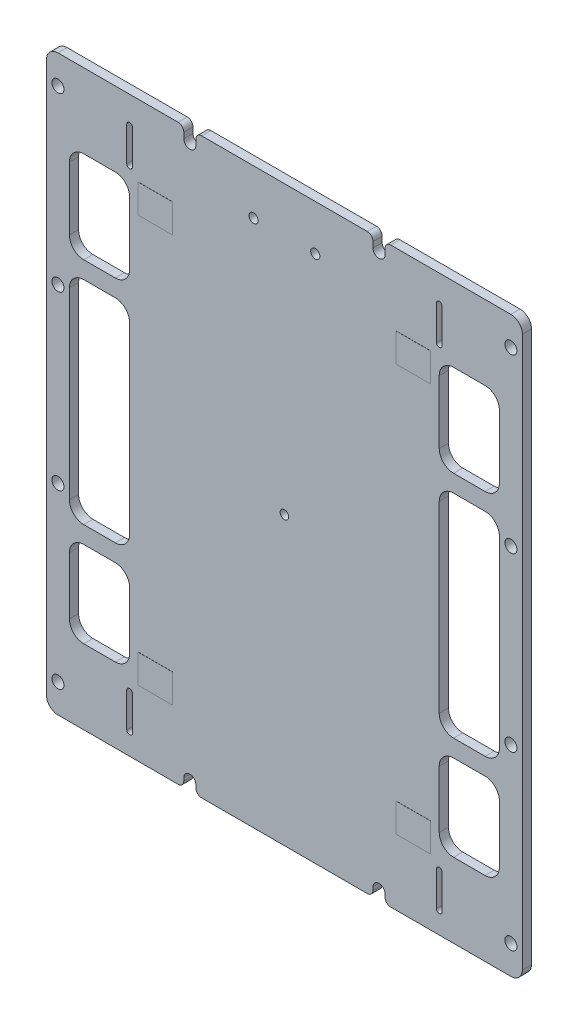
SolidWorks part; units mm, degrees
material "FR4_stuffedProtoboard"
ref_plane "Front Plane" through (0, 0, 0) normal (0, 0, 1) x (1, 0, 0)
ref_plane "Top Plane" through (0, 0, 0) normal (0, 1, 0) x (1, 0, 0)
ref_plane "Right Plane" through (0, 0, 0) normal (1, 0, 0) x (0, 0, -1)
sketch "Sketch1" plane through (0, 0, 0) normal (0, 0, 1) x (1, 0, 0)
  line L1 (-39.5, -50) -> (39.5, -50)
  line L2 (-41.5, -48) -> (-41.5, 48)
  line L3 (-39.5, 50) -> (39.5, 50)
  line L4 (41.5, -48) -> (41.5, 48)
  line L5 (-41.5, -50) -> (41.5, 50) construction
  line L6 (-41.5, 50) -> (41.5, -50) construction
  arc A0 (-39.5, -50) -> (-41.5, -48) centre (-39.5, -48) cw
  arc A1 (39.5, -50) -> (41.5, -48) centre (39.5, -48) ccw
  arc A2 (39.5, 50) -> (41.5, 48) centre (39.5, 48) cw
  arc A3 (-41.5, 48) -> (-39.5, 50) centre (-39.5, 48) cw
  point P0 (0, 0)
  dimension "D3" = 2
  dimension "D1" = 100
  dimension "D2" = 83
extrude "boardOutline" add sketch "Sketch1" along normal blind 1.6
sketch "Sketch2" plane through (0, 0, 1.6) normal (0, 0, 1) x (1, 0, 0)
  line L0 (39.5, 50) -> (-39.5, 50) construction
  line L1 (-41.5, 48) -> (-41.5, -48) construction
  line L2 (-5.385, 42.1) -> (5.385, 42.1) construction
  line L3 (-38, 44.2) -> (-38, 4.2) construction
  line L4 (0, 42.1) -> (0, 50) construction
  circle A0 centre (0, 0) radius 0.75
  circle A1 centre (-38, 44.2) radius 1.05 construction
  circle A2 centre (37.5, 44.2) radius 1.05 construction
  circle A3 centre (37.5, 4.2) radius 1.05 construction
  circle A4 centre (37.5, -35.8) radius 1.05 construction
  circle A5 centre (-38, 4.2) radius 1.05 construction
  circle A6 centre (-38, -35.8) radius 1.05 construction
  circle A7 centre (-5.385, 42.1) radius 0.8
  circle A8 centre (5.385, 42.1) radius 0.8
  dimension "D1" = 1.5
  dimension "D2" = 2.1
  dimension "D9" = 10.77
  dimension "D7" = 1.6
  dimension "D11" = 7.9
  dimension "D3" = 5.8
  dimension "D4" = 3.5
  dimension "D8" = 40
  dimension "D10" = 37.5
  dimension "D5" = 2
  dimension "D6" = 3
extrude "componentHoles" cut sketch "Sketch2" against normal through all
sketch "Sketch4" plane through (0, 0, 1.6) normal (0, 0, 1) x (1, 0, 0)
  line L0 (-27, 39.25) -> (-27, 45.25) construction
  line L1 (-27.5, 39.25) -> (-27.5, 45.25)
  line L2 (-26.5, 39.25) -> (-26.5, 45.25)
  line L3 (39.5, 50) -> (-39.5, 50) construction
  line L4 (-41.5, 48) -> (-41.5, -48) construction
  line L5 (27, 39.25) -> (27, 45.25) construction
  line L6 (26.5, 39.25) -> (26.5, 45.25)
  line L7 (27.5, 39.25) -> (27.5, 45.25)
  line L8 (27, -46.25) -> (27, -40.25) construction
  line L9 (26.5, -46.25) -> (26.5, -40.25)
  line L10 (27.5, -46.25) -> (27.5, -40.25)
  line L11 (-27, -46.25) -> (-27, -40.25) construction
  line L12 (-27.5, -46.25) -> (-27.5, -40.25)
  line L13 (-26.5, -46.25) -> (-26.5, -40.25)
  line L14 (-27, 39.25) -> (27, 39.25) construction
  line L15 (0, 39.25) -> (0, 50) construction
  arc A0 (-27.5, 39.25) -> (-26.5, 39.25) centre (-27, 39.25) ccw
  arc A1 (-26.5, 45.25) -> (-27.5, 45.25) centre (-27, 45.25) ccw
  arc A2 (26.5, 39.25) -> (27.5, 39.25) centre (27, 39.25) ccw
  arc A3 (27.5, 45.25) -> (26.5, 45.25) centre (27, 45.25) ccw
  arc A4 (26.5, -46.25) -> (27.5, -46.25) centre (27, -46.25) ccw
  arc A5 (27.5, -40.25) -> (26.5, -40.25) centre (27, -40.25) ccw
  arc A6 (-27.5, -46.25) -> (-26.5, -46.25) centre (-27, -46.25) ccw
  arc A7 (-26.5, -40.25) -> (-27.5, -40.25) centre (-27, -40.25) ccw
  point P2 (-27, 42.25)
  point P16 (27, 42.25)
  point P23 (27, -43.25)
  point P30 (-27, -43.25)
  dimension "D1" = 4.75
  dimension "D2" = 14
  dimension "D3" = 1
  dimension "D4" = 6
  dimension "D7" = 54
  dimension "D9" = 79.5
  dimension "D5" = 2
  dimension "D6" = 2
extrude "solarCellContactHoles" cut sketch "Sketch4" against normal blind 1.6
sketch "FrameLattice" plane through (0, 0, 0) normal (0, 0, 1) x (1, 0, 0)
  line L4 (-12.5, -19) -> (12.5, -19)
  line L5 (15, -16.5) -> (15, 15.5)
  line L6 (12.5, 18) -> (-12.5, 18)
  line L7 (-15, 15.5) -> (-15, -16.5)
  line L8 (-12.5, -19) -> (12.5, -19)
  line L9 (15, -16.5) -> (15, 15.5)
  line L10 (12.5, 18) -> (-12.5, 18)
  line L11 (-15, 15.5) -> (-15, -16.5)
  line L12 (-12.5, -92) -> (12.5, -92)
  line L13 (15, -89.5) -> (15, -69.5)
  line L14 (12.5, -67) -> (-12.5, -67)
  line L15 (-15, -69.5) -> (-15, -89.5)
  line L16 (-12.5, -92) -> (12.5, -92)
  line L17 (15, -89.5) -> (15, -69.5)
  line L18 (12.5, -67) -> (-12.5, -67)
  line L19 (-15, -69.5) -> (-15, -89.5)
  line L20 (-35, -132) -> (-20.5, -132)
  line L21 (-18, -129.5) -> (-18, -97.5)
  line L22 (-20.5, -95) -> (-35, -95)
  line L23 (-37.5, -97.5) -> (-37.5, -129.5)
  line L24 (-35, -132) -> (-20.5, -132)
  line L25 (-18, -129.5) -> (-18, -97.5)
  line L26 (-20.5, -95) -> (-35, -95)
  line L27 (-37.5, -97.5) -> (-37.5, -129.5)
  line L28 (20.5, -160) -> (35, -160)
  line L29 (37.5, -157.5) -> (37.5, -137.5)
  line L30 (35, -135) -> (20.5, -135)
  line L31 (18, -137.5) -> (18, -157.5)
  line L32 (20.5, -160) -> (35, -160)
  line L33 (37.5, -157.5) -> (37.5, -137.5)
  line L34 (35, -135) -> (20.5, -135)
  line L35 (18, -137.5) -> (18, -157.5)
  line L36 (20.5, -92) -> (35, -92)
  line L37 (37.5, -89.5) -> (37.5, -69.5)
  line L38 (35, -67) -> (20.5, -67)
  line L39 (18, -69.5) -> (18, -89.5)
  line L40 (20.5, -92) -> (35, -92)
  line L41 (37.5, -89.5) -> (37.5, -69.5)
  line L42 (35, -67) -> (20.5, -67)
  line L43 (18, -69.5) -> (18, -89.5)
  line L44 (-35, -92) -> (-20.5, -92)
  line L45 (-18, -89.5) -> (-18, -69.5)
  line L46 (-20.5, -67) -> (-35, -67)
  line L47 (-37.5, -69.5) -> (-37.5, -89.5)
  line L48 (-35, -92) -> (-20.5, -92)
  line L49 (-18, -89.5) -> (-18, -69.5)
  line L50 (-20.5, -67) -> (-35, -67)
  line L51 (-37.5, -69.5) -> (-37.5, -89.5)
  line L52 (20.5, -132) -> (35, -132)
  line L53 (37.5, -129.5) -> (37.5, -97.5)
  line L54 (35, -95) -> (20.5, -95)
  line L55 (18, -97.5) -> (18, -129.5)
  line L56 (20.5, -132) -> (35, -132)
  line L57 (37.5, -129.5) -> (37.5, -97.5)
  line L58 (35, -95) -> (20.5, -95)
  line L59 (18, -97.5) -> (18, -129.5)
  line L60 (-12.5, -160) -> (12.5, -160)
  line L61 (15, -157.5) -> (15, -137.5)
  line L62 (12.5, -135) -> (-12.5, -135)
  line L63 (-15, -137.5) -> (-15, -157.5)
  line L65 (15, -157.5) -> (15, -137.5)
  line L66 (12.5, -135) -> (-12.5, -135)
  line L67 (-15, -137.5) -> (-15, -157.5)
  line L68 (-26.75, -61.5) -> (-26.75, -52.5)
  line L69 (-29.25, -50) -> (-34.5, -50)
  line L70 (-37, -52.5) -> (-37, -61.5)
  line L71 (-34.5, -64) -> (-29.25, -64)
  line L72 (-26.75, -61.5) -> (-26.75, -52.5)
  line L73 (-29.25, -50) -> (-34.5, -50)
  line L74 (-37, -52.5) -> (-37, -61.5)
  line L75 (-34.5, -64) -> (-29.25, -64)
  line L76 (-35, -160) -> (-20.5, -160)
  line L77 (-18, -157.5) -> (-18, -137.5)
  line L78 (-20.5, -135) -> (-35, -135)
  line L79 (-37.5, -137.5) -> (-37.5, -157.5)
  line L80 (-35, -160) -> (-20.5, -160)
  line L81 (-18, -157.5) -> (-18, -137.5)
  line L82 (-20.5, -135) -> (-35, -135)
  line L83 (-37.5, -137.5) -> (-37.5, -157.5)
  line L84 (-12.5, -132) -> (12.5, -132)
  line L85 (15, -129.5) -> (15, -97.5)
  line L86 (12.5, -95) -> (-12.5, -95)
  line L87 (-15, -97.5) -> (-15, -129.5)
  line L88 (-12.5, -132) -> (12.5, -132)
  line L89 (15, -129.5) -> (15, -97.5)
  line L90 (12.5, -95) -> (-12.5, -95)
  line L91 (-15, -97.5) -> (-15, -129.5)
  line L92 (-35, -19) -> (-20.5, -19)
  line L93 (-18, -16.5) -> (-18, 15.5)
  line L94 (-20.5, 18) -> (-35, 18)
  line L95 (-37.5, 15.5) -> (-37.5, -16.5)
  line L96 (-35, -19) -> (-20.5, -19)
  line L97 (-18, -16.5) -> (-18, 15.5)
  line L98 (-20.5, 18) -> (-35, 18)
  line L99 (-37.5, 15.5) -> (-37.5, -16.5)
  line L100 (20.5, -47) -> (35, -47)
  line L101 (37.5, -44.5) -> (37.5, -24.5)
  line L102 (35, -22) -> (20.5, -22)
  line L103 (18, -24.5) -> (18, -44.5)
  line L104 (20.5, -47) -> (35, -47)
  line L105 (37.5, -44.5) -> (37.5, -24.5)
  line L106 (35, -22) -> (20.5, -22)
  line L107 (18, -24.5) -> (18, -44.5)
  line L108 (-12.5, -47) -> (12.5, -47)
  line L109 (15, -44.5) -> (15, -24.5)
  line L110 (12.5, -22) -> (-12.5, -22)
  line L111 (-15, -24.5) -> (-15, -44.5)
  line L112 (-12.5, -47) -> (12.5, -47)
  line L113 (15, -44.5) -> (15, -24.5)
  line L114 (12.5, -22) -> (-12.5, -22)
  line L115 (-15, -24.5) -> (-15, -44.5)
  line L116 (-35, -47) -> (-20.5, -47)
  line L117 (-18, -44.5) -> (-18, -24.5)
  line L118 (-20.5, -22) -> (-35, -22)
  line L119 (-37.5, -24.5) -> (-37.5, -44.5)
  line L120 (-35, -47) -> (-20.5, -47)
  line L121 (-18, -44.5) -> (-18, -24.5)
  line L122 (-20.5, -22) -> (-35, -22)
  line L123 (-37.5, -24.5) -> (-37.5, -44.5)
  line L124 (20.5, -19) -> (35, -19)
  line L125 (37.5, -16.5) -> (37.5, 15.5)
  line L126 (35, 18) -> (20.5, 18)
  line L127 (18, 15.5) -> (18, -16.5)
  line L128 (20.5, -19) -> (35, -19)
  line L129 (37.5, -16.5) -> (37.5, 15.5)
  line L130 (35, 18) -> (20.5, 18)
  line L131 (18, 15.5) -> (18, -16.5)
  line L132 (-35, 21) -> (-20.5, 21)
  line L133 (-18, 23.5) -> (-18, 43.5)
  line L134 (-20.5, 46) -> (-35, 46)
  line L135 (-37.5, 43.5) -> (-37.5, 23.5)
  line L136 (-35, 21) -> (-20.5, 21)
  line L137 (-18, 23.5) -> (-18, 43.5)
  line L138 (-20.5, 46) -> (-35, 46)
  line L139 (-37.5, 43.5) -> (-37.5, 23.5)
  line L140 (-12.5, 21) -> (12.5, 21)
  line L141 (15, 23.5) -> (15, 43.5)
  line L142 (12.5, 46) -> (-12.5, 46)
  line L143 (-15, 43.5) -> (-15, 23.5)
  line L144 (-12.5, 21) -> (12.5, 21)
  line L145 (15, 23.5) -> (15, 43.5)
  line L147 (-15, 43.5) -> (-15, 23.5)
  line L148 (20.5, 21) -> (35, 21)
  line L149 (37.5, 23.5) -> (37.5, 43.5)
  line L150 (35, 46) -> (20.5, 46)
  line L151 (18, 43.5) -> (18, 23.5)
  line L152 (20.5, 21) -> (35, 21)
  line L153 (37.5, 23.5) -> (37.5, 43.5)
  line L154 (35, 46) -> (20.5, 46)
  line L155 (18, 43.5) -> (18, 23.5)
  line L156 (-3.5, -61.5) -> (-3.5, -52.5)
  line L157 (-6, -50) -> (-12.5, -50)
  line L158 (-15, -52.5) -> (-15, -61.5)
  line L159 (-12.5, -64) -> (-6, -64)
  line L160 (-3.5, -61.5) -> (-3.5, -52.5)
  line L161 (-6, -50) -> (-12.5, -50)
  line L162 (-15, -52.5) -> (-15, -61.5)
  line L163 (-12.5, -64) -> (-6, -64)
  line L164 (29.25, -64) -> (34.5, -64)
  line L165 (37, -61.5) -> (37, -52.5)
  line L166 (34.5, -50) -> (29.25, -50)
  line L167 (26.75, -52.5) -> (26.75, -61.5)
  line L168 (29.25, -64) -> (34.5, -64)
  line L169 (37, -61.5) -> (37, -52.5)
  line L170 (34.5, -50) -> (29.25, -50)
  line L171 (26.75, -52.5) -> (26.75, -61.5)
  line L172 (6, -64) -> (12.5, -64)
  line L173 (15, -61.5) -> (15, -52.5)
  line L174 (12.5, -50) -> (6, -50)
  line L175 (3.5, -52.5) -> (3.5, -61.5)
  line L176 (6, -64) -> (12.5, -64)
  line L177 (15, -61.5) -> (15, -52.5)
  line L178 (12.5, -50) -> (6, -50)
  line L179 (3.5, -52.5) -> (3.5, -61.5)
  line L212 (-12.5, -160) -> (12.5, -160)
  line L213 (12.5, 46) -> (-12.5, 46)
  circle A2 centre (-16.5, 48) radius 0.8
  circle A3 centre (-16.5, 48) radius 0.8
  circle A4 centre (-16.5, -162) radius 0.8
  arc A5 (12.5, -19) -> (15, -16.5) centre (12.5, -16.5) ccw
  arc A6 (15, 15.5) -> (12.5, 18) centre (12.5, 15.5) ccw
  arc A7 (-12.5, 18) -> (-15, 15.5) centre (-12.5, 15.5) ccw
  arc A8 (-15, -16.5) -> (-12.5, -19) centre (-12.5, -16.5) ccw
  arc A9 (12.5, -19) -> (15, -16.5) centre (12.5, -16.5) ccw
  arc A10 (15, 15.5) -> (12.5, 18) centre (12.5, 15.5) ccw
  arc A11 (-12.5, 18) -> (-15, 15.5) centre (-12.5, 15.5) ccw
  arc A12 (-15, -16.5) -> (-12.5, -19) centre (-12.5, -16.5) ccw
  arc A13 (12.5, -92) -> (15, -89.5) centre (12.5, -89.5) ccw
  arc A14 (15, -69.5) -> (12.5, -67) centre (12.5, -69.5) ccw
  arc A15 (-12.5, -67) -> (-15, -69.5) centre (-12.5, -69.5) ccw
  arc A16 (-15, -89.5) -> (-12.5, -92) centre (-12.5, -89.5) ccw
  arc A17 (12.5, -92) -> (15, -89.5) centre (12.5, -89.5) ccw
  arc A18 (15, -69.5) -> (12.5, -67) centre (12.5, -69.5) ccw
  arc A19 (-12.5, -67) -> (-15, -69.5) centre (-12.5, -69.5) ccw
  arc A20 (-15, -89.5) -> (-12.5, -92) centre (-12.5, -89.5) ccw
  arc A21 (-20.5, -132) -> (-18, -129.5) centre (-20.5, -129.5) ccw
  arc A22 (-18, -97.5) -> (-20.5, -95) centre (-20.5, -97.5) ccw
  arc A23 (-35, -95) -> (-37.5, -97.5) centre (-35, -97.5) ccw
  arc A24 (-37.5, -129.5) -> (-35, -132) centre (-35, -129.5) ccw
  arc A25 (-20.5, -132) -> (-18, -129.5) centre (-20.5, -129.5) ccw
  arc A26 (-18, -97.5) -> (-20.5, -95) centre (-20.5, -97.5) ccw
  arc A27 (-35, -95) -> (-37.5, -97.5) centre (-35, -97.5) ccw
  arc A28 (-37.5, -129.5) -> (-35, -132) centre (-35, -129.5) ccw
  arc A29 (35, -160) -> (37.5, -157.5) centre (35, -157.5) ccw
  arc A30 (37.5, -137.5) -> (35, -135) centre (35, -137.5) ccw
  arc A31 (20.5, -135) -> (18, -137.5) centre (20.5, -137.5) ccw
  arc A32 (18, -157.5) -> (20.5, -160) centre (20.5, -157.5) ccw
  arc A33 (35, -160) -> (37.5, -157.5) centre (35, -157.5) ccw
  arc A34 (37.5, -137.5) -> (35, -135) centre (35, -137.5) ccw
  arc A35 (20.5, -135) -> (18, -137.5) centre (20.5, -137.5) ccw
  arc A36 (18, -157.5) -> (20.5, -160) centre (20.5, -157.5) ccw
  arc A37 (35, -92) -> (37.5, -89.5) centre (35, -89.5) ccw
  arc A38 (37.5, -69.5) -> (35, -67) centre (35, -69.5) ccw
  arc A39 (20.5, -67) -> (18, -69.5) centre (20.5, -69.5) ccw
  arc A40 (18, -89.5) -> (20.5, -92) centre (20.5, -89.5) ccw
  arc A41 (35, -92) -> (37.5, -89.5) centre (35, -89.5) ccw
  arc A42 (37.5, -69.5) -> (35, -67) centre (35, -69.5) ccw
  arc A43 (20.5, -67) -> (18, -69.5) centre (20.5, -69.5) ccw
  arc A44 (18, -89.5) -> (20.5, -92) centre (20.5, -89.5) ccw
  arc A45 (-20.5, -92) -> (-18, -89.5) centre (-20.5, -89.5) ccw
  arc A46 (-18, -69.5) -> (-20.5, -67) centre (-20.5, -69.5) ccw
  arc A47 (-35, -67) -> (-37.5, -69.5) centre (-35, -69.5) ccw
  arc A48 (-37.5, -89.5) -> (-35, -92) centre (-35, -89.5) ccw
  arc A49 (-20.5, -92) -> (-18, -89.5) centre (-20.5, -89.5) ccw
  arc A50 (-18, -69.5) -> (-20.5, -67) centre (-20.5, -69.5) ccw
  arc A51 (-35, -67) -> (-37.5, -69.5) centre (-35, -69.5) ccw
  arc A52 (-37.5, -89.5) -> (-35, -92) centre (-35, -89.5) ccw
  arc A53 (35, -132) -> (37.5, -129.5) centre (35, -129.5) ccw
  arc A54 (37.5, -97.5) -> (35, -95) centre (35, -97.5) ccw
  arc A55 (20.5, -95) -> (18, -97.5) centre (20.5, -97.5) ccw
  arc A56 (18, -129.5) -> (20.5, -132) centre (20.5, -129.5) ccw
  arc A57 (35, -132) -> (37.5, -129.5) centre (35, -129.5) ccw
  arc A58 (37.5, -97.5) -> (35, -95) centre (35, -97.5) ccw
  arc A59 (20.5, -95) -> (18, -97.5) centre (20.5, -97.5) ccw
  arc A60 (18, -129.5) -> (20.5, -132) centre (20.5, -129.5) ccw
  arc A61 (12.5, -160) -> (15, -157.5) centre (12.5, -157.5) ccw
  arc A62 (15, -137.5) -> (12.5, -135) centre (12.5, -137.5) ccw
  arc A63 (-12.5, -135) -> (-15, -137.5) centre (-12.5, -137.5) ccw
  arc A64 (-15, -157.5) -> (-12.5, -160) centre (-12.5, -157.5) ccw
  arc A65 (12.5, -160) -> (15, -157.5) centre (12.5, -157.5) ccw
  arc A66 (15, -137.5) -> (12.5, -135) centre (12.5, -137.5) ccw
  arc A67 (-12.5, -135) -> (-15, -137.5) centre (-12.5, -137.5) ccw
  arc A68 (-15, -157.5) -> (-12.5, -160) centre (-12.5, -157.5) ccw
  circle A69 centre (-16.5, -162) radius 0.8
  circle A70 centre (16.5, -162) radius 0.8
  circle A71 centre (16.5, -162) radius 0.8
  circle A72 centre (-16.5, -65.5) radius 0.8
  circle A73 centre (-16.5, -65.5) radius 0.8
  circle A74 centre (16.5, -65.5) radius 0.8
  circle A75 centre (16.5, -65.5) radius 0.8
  circle A76 centre (-39.5, -129) radius 0.8
  circle A77 centre (-39.5, -129) radius 0.8
  circle A78 centre (39.5, -159) radius 0.8
  circle A79 centre (39.5, -159) radius 0.8
  circle A80 centre (-39.5, -159) radius 0.8
  circle A81 centre (-39.5, -159) radius 0.8
  circle A82 centre (39.5, -129) radius 0.8
  circle A83 centre (39.5, -129) radius 0.8
  circle A84 centre (39.5, -99) radius 0.8
  circle A85 centre (39.5, -99) radius 0.8
  circle A86 centre (-39.5, -99) radius 0.8
  circle A87 centre (-39.5, -99) radius 0.8
  circle A88 centre (-39.5, -69) radius 0.8
  circle A89 centre (-39.5, -69) radius 0.8
  circle A90 centre (39.5, -69) radius 0.8
  circle A91 centre (39.5, -69) radius 0.8
  circle A92 centre (39.5, -15) radius 0.8
  circle A93 centre (39.5, -15) radius 0.8
  circle A94 centre (39.5, 15) radius 0.8
  arc A95 (-26.75, -52.5) -> (-29.25, -50) centre (-29.25, -52.5) ccw
  arc A96 (-34.5, -50) -> (-37, -52.5) centre (-34.5, -52.5) ccw
  arc A97 (-37, -61.5) -> (-34.5, -64) centre (-34.5, -61.5) ccw
  arc A98 (-29.25, -64) -> (-26.75, -61.5) centre (-29.25, -61.5) ccw
  arc A99 (-26.75, -52.5) -> (-29.25, -50) centre (-29.25, -52.5) ccw
  arc A100 (-34.5, -50) -> (-37, -52.5) centre (-34.5, -52.5) ccw
  arc A101 (-37, -61.5) -> (-34.5, -64) centre (-34.5, -61.5) ccw
  arc A102 (-29.25, -64) -> (-26.75, -61.5) centre (-29.25, -61.5) ccw
  arc A103 (-20.5, -160) -> (-18, -157.5) centre (-20.5, -157.5) ccw
  arc A104 (-18, -137.5) -> (-20.5, -135) centre (-20.5, -137.5) ccw
  arc A105 (-35, -135) -> (-37.5, -137.5) centre (-35, -137.5) ccw
  arc A106 (-37.5, -157.5) -> (-35, -160) centre (-35, -157.5) ccw
  arc A107 (-20.5, -160) -> (-18, -157.5) centre (-20.5, -157.5) ccw
  arc A108 (-18, -137.5) -> (-20.5, -135) centre (-20.5, -137.5) ccw
  arc A109 (-35, -135) -> (-37.5, -137.5) centre (-35, -137.5) ccw
  arc A110 (-37.5, -157.5) -> (-35, -160) centre (-35, -157.5) ccw
  arc A111 (12.5, -132) -> (15, -129.5) centre (12.5, -129.5) ccw
  arc A112 (15, -97.5) -> (12.5, -95) centre (12.5, -97.5) ccw
  arc A113 (-12.5, -95) -> (-15, -97.5) centre (-12.5, -97.5) ccw
  arc A114 (-15, -129.5) -> (-12.5, -132) centre (-12.5, -129.5) ccw
  arc A115 (12.5, -132) -> (15, -129.5) centre (12.5, -129.5) ccw
  arc A116 (15, -97.5) -> (12.5, -95) centre (12.5, -97.5) ccw
  arc A117 (-12.5, -95) -> (-15, -97.5) centre (-12.5, -97.5) ccw
  arc A118 (-15, -129.5) -> (-12.5, -132) centre (-12.5, -129.5) ccw
  arc A119 (-20.5, -19) -> (-18, -16.5) centre (-20.5, -16.5) ccw
  arc A120 (-18, 15.5) -> (-20.5, 18) centre (-20.5, 15.5) ccw
  arc A121 (-35, 18) -> (-37.5, 15.5) centre (-35, 15.5) ccw
  arc A122 (-37.5, -16.5) -> (-35, -19) centre (-35, -16.5) ccw
  arc A123 (-20.5, -19) -> (-18, -16.5) centre (-20.5, -16.5) ccw
  arc A124 (-18, 15.5) -> (-20.5, 18) centre (-20.5, 15.5) ccw
  arc A125 (-35, 18) -> (-37.5, 15.5) centre (-35, 15.5) ccw
  arc A126 (-37.5, -16.5) -> (-35, -19) centre (-35, -16.5) ccw
  arc A127 (35, -47) -> (37.5, -44.5) centre (35, -44.5) ccw
  arc A128 (37.5, -24.5) -> (35, -22) centre (35, -24.5) ccw
  arc A129 (20.5, -22) -> (18, -24.5) centre (20.5, -24.5) ccw
  arc A130 (18, -44.5) -> (20.5, -47) centre (20.5, -44.5) ccw
  arc A131 (35, -47) -> (37.5, -44.5) centre (35, -44.5) ccw
  arc A132 (37.5, -24.5) -> (35, -22) centre (35, -24.5) ccw
  arc A133 (20.5, -22) -> (18, -24.5) centre (20.5, -24.5) ccw
  arc A134 (18, -44.5) -> (20.5, -47) centre (20.5, -44.5) ccw
  arc A135 (12.5, -47) -> (15, -44.5) centre (12.5, -44.5) ccw
  arc A136 (15, -24.5) -> (12.5, -22) centre (12.5, -24.5) ccw
  arc A137 (-12.5, -22) -> (-15, -24.5) centre (-12.5, -24.5) ccw
  arc A138 (-15, -44.5) -> (-12.5, -47) centre (-12.5, -44.5) ccw
  arc A139 (12.5, -47) -> (15, -44.5) centre (12.5, -44.5) ccw
  arc A140 (15, -24.5) -> (12.5, -22) centre (12.5, -24.5) ccw
  arc A141 (-12.5, -22) -> (-15, -24.5) centre (-12.5, -24.5) ccw
  arc A142 (-15, -44.5) -> (-12.5, -47) centre (-12.5, -44.5) ccw
  arc A143 (-20.5, -47) -> (-18, -44.5) centre (-20.5, -44.5) ccw
  arc A144 (-18, -24.5) -> (-20.5, -22) centre (-20.5, -24.5) ccw
  arc A145 (-35, -22) -> (-37.5, -24.5) centre (-35, -24.5) ccw
  arc A146 (-37.5, -44.5) -> (-35, -47) centre (-35, -44.5) ccw
  arc A147 (-20.5, -47) -> (-18, -44.5) centre (-20.5, -44.5) ccw
  arc A148 (-18, -24.5) -> (-20.5, -22) centre (-20.5, -24.5) ccw
  arc A149 (-35, -22) -> (-37.5, -24.5) centre (-35, -24.5) ccw
  arc A150 (-37.5, -44.5) -> (-35, -47) centre (-35, -44.5) ccw
  arc A151 (35, -19) -> (37.5, -16.5) centre (35, -16.5) ccw
  arc A152 (37.5, 15.5) -> (35, 18) centre (35, 15.5) ccw
  arc A153 (20.5, 18) -> (18, 15.5) centre (20.5, 15.5) ccw
  arc A154 (18, -16.5) -> (20.5, -19) centre (20.5, -16.5) ccw
  arc A155 (35, -19) -> (37.5, -16.5) centre (35, -16.5) ccw
  arc A156 (37.5, 15.5) -> (35, 18) centre (35, 15.5) ccw
  arc A157 (20.5, 18) -> (18, 15.5) centre (20.5, 15.5) ccw
  arc A158 (18, -16.5) -> (20.5, -19) centre (20.5, -16.5) ccw
  arc A159 (-20.5, 21) -> (-18, 23.5) centre (-20.5, 23.5) ccw
  arc A160 (-18, 43.5) -> (-20.5, 46) centre (-20.5, 43.5) ccw
  arc A161 (-35, 46) -> (-37.5, 43.5) centre (-35, 43.5) ccw
  arc A162 (-37.5, 23.5) -> (-35, 21) centre (-35, 23.5) ccw
  arc A163 (-20.5, 21) -> (-18, 23.5) centre (-20.5, 23.5) ccw
  arc A164 (-18, 43.5) -> (-20.5, 46) centre (-20.5, 43.5) ccw
  arc A165 (-35, 46) -> (-37.5, 43.5) centre (-35, 43.5) ccw
  arc A166 (-37.5, 23.5) -> (-35, 21) centre (-35, 23.5) ccw
  arc A167 (12.5, 21) -> (15, 23.5) centre (12.5, 23.5) ccw
  arc A168 (15, 43.5) -> (12.5, 46) centre (12.5, 43.5) ccw
  arc A169 (-12.5, 46) -> (-15, 43.5) centre (-12.5, 43.5) ccw
  arc A170 (-15, 23.5) -> (-12.5, 21) centre (-12.5, 23.5) ccw
  arc A171 (12.5, 21) -> (15, 23.5) centre (12.5, 23.5) ccw
  arc A172 (15, 43.5) -> (12.5, 46) centre (12.5, 43.5) ccw
  arc A173 (-12.5, 46) -> (-15, 43.5) centre (-12.5, 43.5) ccw
  arc A174 (-15, 23.5) -> (-12.5, 21) centre (-12.5, 23.5) ccw
  arc A175 (35, 21) -> (37.5, 23.5) centre (35, 23.5) ccw
  arc A176 (37.5, 43.5) -> (35, 46) centre (35, 43.5) ccw
  arc A177 (20.5, 46) -> (18, 43.5) centre (20.5, 43.5) ccw
  arc A178 (18, 23.5) -> (20.5, 21) centre (20.5, 23.5) ccw
  arc A179 (35, 21) -> (37.5, 23.5) centre (35, 23.5) ccw
  arc A180 (37.5, 43.5) -> (35, 46) centre (35, 43.5) ccw
  arc A181 (20.5, 46) -> (18, 43.5) centre (20.5, 43.5) ccw
  arc A182 (18, 23.5) -> (20.5, 21) centre (20.5, 23.5) ccw
  circle A183 centre (39.5, 15) radius 0.8
  circle A184 centre (-39.5, 45) radius 0.8
  circle A185 centre (-39.5, 45) radius 0.8
  circle A186 centre (39.5, 45) radius 0.8
  circle A187 centre (39.5, 45) radius 0.8
  circle A188 centre (-39.5, 15) radius 0.8
  circle A189 centre (-39.5, 15) radius 0.8
  circle A190 centre (16.5, -48.5) radius 0.8
  circle A191 centre (16.5, -48.5) radius 0.8
  circle A192 centre (-16.5, -48.5) radius 0.8
  circle A193 centre (-16.5, -48.5) radius 0.8
  circle A194 centre (16.5, 48) radius 0.8
  circle A195 centre (16.5, 48) radius 0.8
  circle A196 centre (-39.5, -15) radius 0.8
  circle A197 centre (-39.5, -15) radius 0.8
  circle A198 centre (-22, -61) radius 2.75
  circle A199 centre (-22, -61) radius 2.75
  circle A200 centre (-22, -53) radius 2.75
  circle A201 centre (-22, -53) radius 2.75
  circle A202 centre (22, -53) radius 2.75
  circle A203 centre (22, -53) radius 2.75
  circle A204 centre (22, -61) radius 2.75
  arc A205 (-3.5, -52.5) -> (-6, -50) centre (-6, -52.5) ccw
  arc A206 (-12.5, -50) -> (-15, -52.5) centre (-12.5, -52.5) ccw
  arc A207 (-15, -61.5) -> (-12.5, -64) centre (-12.5, -61.5) ccw
  arc A208 (-6, -64) -> (-3.5, -61.5) centre (-6, -61.5) ccw
  arc A209 (-3.5, -52.5) -> (-6, -50) centre (-6, -52.5) ccw
  arc A210 (-12.5, -50) -> (-15, -52.5) centre (-12.5, -52.5) ccw
  arc A211 (-15, -61.5) -> (-12.5, -64) centre (-12.5, -61.5) ccw
  arc A212 (-6, -64) -> (-3.5, -61.5) centre (-6, -61.5) ccw
  circle A213 centre (22, -61) radius 2.75
  circle A214 centre (0, -57) radius 2.75
  circle A215 centre (0, -57) radius 2.75
  circle A216 centre (39.5, -45) radius 0.8
  circle A217 centre (39.5, -45) radius 0.8
  circle A218 centre (-39.5, -45) radius 0.8
  arc A219 (34.5, -64) -> (37, -61.5) centre (34.5, -61.5) ccw
  arc A220 (37, -52.5) -> (34.5, -50) centre (34.5, -52.5) ccw
  arc A221 (29.25, -50) -> (26.75, -52.5) centre (29.25, -52.5) ccw
  arc A222 (26.75, -61.5) -> (29.25, -64) centre (29.25, -61.5) ccw
  arc A223 (34.5, -64) -> (37, -61.5) centre (34.5, -61.5) ccw
  arc A224 (37, -52.5) -> (34.5, -50) centre (34.5, -52.5) ccw
  arc A225 (29.25, -50) -> (26.75, -52.5) centre (29.25, -52.5) ccw
  arc A226 (26.75, -61.5) -> (29.25, -64) centre (29.25, -61.5) ccw
  arc A227 (12.5, -64) -> (15, -61.5) centre (12.5, -61.5) ccw
  arc A228 (15, -52.5) -> (12.5, -50) centre (12.5, -52.5) ccw
  arc A229 (6, -50) -> (3.5, -52.5) centre (6, -52.5) ccw
  arc A230 (3.5, -61.5) -> (6, -64) centre (6, -61.5) ccw
  arc A231 (12.5, -64) -> (15, -61.5) centre (12.5, -61.5) ccw
  arc A232 (15, -52.5) -> (12.5, -50) centre (12.5, -52.5) ccw
  arc A233 (6, -50) -> (3.5, -52.5) centre (6, -52.5) ccw
  arc A234 (3.5, -61.5) -> (6, -64) centre (6, -61.5) ccw
  circle A235 centre (-39.5, -45) radius 0.8
  dimension "D1" = 0
  dimension "D2" = 0
  dimension "D3" = 0
  dimension "D4" = 0
  dimension "D5" = 0
  dimension "D6" = 0
  dimension "D7" = 0
  dimension "D8" = 0
  dimension "D9" = 0
  dimension "D10" = 0
  dimension "D11" = 0
  dimension "D12" = 0
  dimension "D13" = 0
  dimension "D14" = 0
  dimension "D15" = 0
  dimension "D16" = 0
  dimension "D17" = 0
  dimension "D18" = 0
  dimension "D19" = 0
  dimension "D20" = 0
  dimension "D21" = 0
  dimension "D22" = 0
  dimension "D23" = 0
  dimension "D24" = 0
  dimension "D25" = 0
  dimension "D26" = 0
  dimension "D27" = 0
  dimension "D28" = 0
  dimension "D29" = 0
  dimension "D30" = 0
  dimension "D31" = 0
  dimension "D32" = 0
  dimension "D33" = 0
  dimension "D34" = 0
  dimension "D35" = 0
  dimension "D36" = 0
  dimension "D37" = 0
  dimension "D38" = 0
  dimension "D39" = 0
  dimension "D40" = 0
  dimension "D41" = 0
  dimension "D42" = 0
  dimension "D43" = 0
  dimension "D44" = 0
  dimension "D45" = 0
  dimension "D46" = 0
  dimension "D47" = 0
  dimension "D48" = 0
  dimension "D49" = 0
  dimension "D50" = 0
  dimension "D51" = 0
sketch "Sketch3" plane through (0, 0, 1.6) normal (0, 0, 1) x (1, 0, 0)
  line L0 (-35, -19) -> (-20.5, -19) construction
  line L1 (-35, 37) -> (-29.5, 37)
  line L2 (-37.5, 34.5) -> (-37.5, 23.5)
  line L3 (-35, 21) -> (-29.5, 21)
  line L4 (-27, 34.5) -> (-27, 23.5)
  line L6 (-29.5, -22) -> (-35, -22)
  line L7 (-37.5, 15.5) -> (-37.5, -16.5) construction
  line L8 (-20.5, -22) -> (-35, -22) construction
  line L9 (0, 50) -> (0, -50) construction
  line L10 (39.5, 50) -> (-39.5, 50) construction
  line L11 (-39.5, -50) -> (39.5, -50) construction
  line L12 (-27, -24.5) -> (-27, -34.5)
  line L13 (-29.5, -37) -> (-35, -37)
  line L14 (-37.5, -24.5) -> (-37.5, -34.5)
  line L15 (-20.5, 18) -> (-35, 18) construction
  line L16 (-35, 21) -> (-20.5, 21) construction
  line L19 (-29.5, -19) -> (-35, -19)
  line L25 (-27, -16.5) -> (-27, 15.5)
  line L26 (-29.5, 18) -> (-35, 18)
  line L27 (-37.5, -16.5) -> (-37.5, 15.5)
  arc A0 (-37.5, 23.5) -> (-35, 21) centre (-35, 23.5) ccw
  arc A1 (-29.5, 21) -> (-27, 23.5) centre (-29.5, 23.5) ccw
  arc A2 (-29.5, 37) -> (-27, 34.5) centre (-29.5, 34.5) cw
  arc A3 (-35, 37) -> (-37.5, 34.5) centre (-35, 34.5) ccw
  arc A4 (-29.5, -19) -> (-27, -16.5) centre (-29.5, -16.5) ccw
  arc A5 (-27, -34.5) -> (-29.5, -37) centre (-29.5, -34.5) cw
  arc A6 (-35, -37) -> (-37.5, -34.5) centre (-35, -34.5) cw
  arc A7 (-35, -22) -> (-37.5, -24.5) centre (-35, -24.5) ccw
  arc A8 (-29.5, -22) -> (-27, -24.5) centre (-29.5, -24.5) cw
  arc A9 (-37.5, 23.5) -> (-35, 21) centre (-35, 23.5) ccw construction
  arc A17 (-35, -19) -> (-37.5, -16.5) centre (-35, -16.5) cw
  arc A18 (-35, 18) -> (-37.5, 15.5) centre (-35, 15.5) ccw
  arc A19 (-27, 15.5) -> (-29.5, 18) centre (-29.5, 15.5) ccw
  point P12 (-27, 21)
  point P15 (-27, 37)
  point P18 (-37.5, 37)
  dimension "D10" = 13
  dimension "D1" = 10.5
  dimension "D3" = 13
extrude "windows_1side" cut sketch "Sketch3" against normal through all
sketch "Sketch5" plane through (0, 0, 1.6) normal (0, 0, 1) x (1, 0, 0)
  line L0 (-41.5, 48) -> (-41.5, -48) construction
  line L1 (-25.5, 37.5) -> (-19.5, 37.5)
  line L2 (-25.5, 37.5) -> (-25.5, 32.5)
  line L3 (-25.5, 32.5) -> (-19.5, 32.5)
  line L4 (-19.5, 37.5) -> (-19.5, 32.5)
  line L5 (0, 37.5) -> (0, 50) construction
  line L6 (19.5, 37.5) -> (19.5, 32.5)
  line L7 (25.5, 37.5) -> (25.5, 32.5)
  line L8 (19.5, 32.5) -> (25.5, 32.5)
  line L9 (19.5, 37.5) -> (25.5, 37.5)
  line L10 (19.5, -33.5) -> (19.5, -38.5)
  line L11 (25.5, -33.5) -> (25.5, -38.5)
  line L12 (19.5, -38.5) -> (25.5, -38.5)
  line L13 (19.5, -33.5) -> (25.5, -33.5)
  line L14 (-25.5, -33.5) -> (-25.5, -38.5)
  line L15 (-19.5, -33.5) -> (-19.5, -38.5)
  line L16 (-25.5, -38.5) -> (-19.5, -38.5)
  line L17 (-25.5, -33.5) -> (-19.5, -33.5)
  line L18 (-19.5, 37.5) -> (19.5, 37.5) construction
  line L19 (-25.5, 37.5) -> (-25.5, -33.5) construction
  line L20 (39.5, 50) -> (-39.5, 50) construction
  arc A0 (-27.5, 39.25) -> (-26.5, 39.25) centre (-27, 39.25) ccw construction
  dimension "D1" = 5
  dimension "D2" = 6
  dimension "D3" = 16
  dimension "D4" = 1.75
  dimension "D7" = 45
  dimension "D8" = 71
  dimension "D5" = 2
  dimension "D6" = 2
extrude "contactPads" add sketch "Sketch5" along normal blind 0.02
hole_wizard "M2 Clearance Hole1" positions "Sketch6" profile "Sketch7" hole size "M2" standard "ANSI Metric" end condition through all
sketch "Sketch6" plane through (0, 0, 0) normal (0, 0, -1) x (-1, 0, 0)
  line L5 (39.5, -50) -> (39.5, -45) construction
  line L6 (39.5, -50) -> (-39.5, -50) construction
  line L7 (39.5, -45) -> (39.5, -15) construction
  line L8 (39.5, -15) -> (39.5, 15) construction
  line L9 (39.5, 15) -> (39.5, 45) construction
  line L10 (39.5, 45) -> (39.5, 50) construction
  line L11 (-39.5, 50) -> (39.5, 50) construction
  line L15 (37.5, -27.0602) -> (41.5, -27.0602) construction
  line L16 (37.5, -24.5) -> (37.5, -34.5) construction
  line L17 (41.5, 48) -> (41.5, -48) construction
  point P0 (39.5, 45)
  point P27 (39.5, -15)
  point P36 (39.5, -45)
  point P38 (39.5, 15)
  point P73 (39.5, -27.0602)
  dimension "D2" = 5
sketch "Sketch7" plane through (-39.5, 45, 0) normal (1, 0, 0) x (0, 1, 0)
  line L0 (0, 0) -> (0, 1.62)
  line L1 (0, 1.62) -> (1.05, 1.62)
  line L2 (1.05, 1.62) -> (1.05, 0)
  line L5 (1.05, 0) -> (0, 0)
  line L11 (0, -6.35) -> (0, 107.95) construction
  dimension "Thru Hole Dia." = 2.1
  dimension "Thru Hole Depth" = 1.62
sketch "Sketch10" plane through (0, 0, 0) normal (0, 0, -1) x (-1, 0, 0)
  line L0 (16.5, 48) -> (16.5, 55.0732) construction
  line L1 (15.45, 48) -> (15.45, 55.0732)
  line L2 (17.55, 48) -> (17.55, 55.0732)
  line L3 (16.5, -48.5) -> (16.5, -55.5732) construction
  line L4 (17.55, -48.5) -> (17.55, -55.5732)
  line L5 (15.45, -48.5) -> (15.45, -55.5732)
  line L6 (41.5, 48) -> (41.5, -48) construction
  line L8 (39.5, -50) -> (-39.5, -50) construction
  line L9 (-39.5, 50) -> (39.5, 50) construction
  arc A0 (15.45, 48) -> (17.55, 48) centre (16.5, 48) ccw
  arc A1 (17.55, 55.0732) -> (15.45, 55.0732) centre (16.5, 55.0732) ccw
  arc A2 (17.55, -48.5) -> (15.45, -48.5) centre (16.5, -48.5) ccw
  arc A3 (15.45, -55.5732) -> (17.55, -55.5732) centre (16.5, -55.5732) ccw
  point P2 (16.5, 51.5366)
  point P7 (16.5, -52.0366)
  dimension "D1" = 1.05
  dimension "D2" = 25
  dimension "D3" = 2
  dimension "D4" = 1.5
extrude "Cut-Extrude1" cut sketch "Sketch10" against normal through all both and the other way through all
fillet "Fillet3" radius 1 4 edges at (-17.55, 50, 0.8) (-15.45, 50, 0.8) (-15.45, -50, 0.8) (-17.55, -50, 0.8)
mirror "Mirror1" about plane through (0, 0, 0) normal (1, 0, 0) of "Cut-Extrude1", "Fillet3", "windows_1side", "M2 Clearance Hole1"
sketch "Wedge Fastener Hole Locations" plane through (0, 0, 0) normal (0, 0, -1) x (-1, 0, 0)
  circle A1 centre (22, 5.4) radius 1.2 construction
  circle A2 centre (22, 5.4) radius 1.2
  circle A3 centre (-22, -4.6) radius 1.2 construction
  circle A4 centre (0, -4.6) radius 1.2 construction
  circle A5 centre (22, -4.6) radius 1.2 construction
  circle A6 centre (-22, -4.6) radius 1.2
  circle A7 centre (0, -4.6) radius 1.2
  circle A8 centre (22, -4.6) radius 1.2
  circle A9 centre (0, 25.4) radius 1.2 construction
  circle A10 centre (22, 25.4) radius 1.2 construction
  circle A11 centre (0, 35.4) radius 1.2 construction
  circle A12 centre (22, 35.4) radius 1.2 construction
  circle A13 centre (0, 25.4) radius 1.2
  circle A14 centre (22, 25.4) radius 1.2
  circle A15 centre (0, 35.4) radius 1.2
  circle A16 centre (22, 35.4) radius 1.2
  circle A17 centre (0, 15.4) radius 1.2 construction
  circle A18 centre (22, 15.4) radius 1.2 construction
  circle A19 centre (-22, 25.4) radius 1.2 construction
  circle A20 centre (-22, 35.4) radius 1.2 construction
  circle A21 centre (0, 15.4) radius 1.2
  circle A22 centre (22, 15.4) radius 1.2
  circle A23 centre (-22, 25.4) radius 1.2
  circle A24 centre (-22, 35.4) radius 1.2
  circle A25 centre (-22, 15.4) radius 1.2 construction
  circle A26 centre (-22, 15.4) radius 1.2
  circle A27 centre (-22, 5.4) radius 1.2 construction
  circle A28 centre (0, 5.4) radius 1.2 construction
  circle A29 centre (-22, 5.4) radius 1.2
  circle A30 centre (0, 5.4) radius 1.2
  circle A31 centre (-22, -24.6) radius 1.2 construction
  circle A32 centre (0, -24.6) radius 1.2 construction
  circle A33 centre (22, -24.6) radius 1.2 construction
  circle A34 centre (-22, -14.6) radius 1.2 construction
  circle A35 centre (0, -14.6) radius 1.2 construction
  circle A36 centre (22, -14.6) radius 1.2 construction
  circle A37 centre (-22, -24.6) radius 1.2
  circle A38 centre (0, -24.6) radius 1.2
  circle A39 centre (22, -24.6) radius 1.2
  circle A40 centre (-22, -14.6) radius 1.2
  circle A41 centre (0, -14.6) radius 1.2
  circle A42 centre (22, -14.6) radius 1.2
  circle A43 centre (-22, -34.6) radius 1.2 construction
  circle A44 centre (0, -34.6) radius 1.2 construction
  circle A45 centre (22, -34.6) radius 1.2 construction
  circle A46 centre (-22, -34.6) radius 1.2
  circle A47 centre (0, -34.6) radius 1.2
  circle A48 centre (22, -34.6) radius 1.2
